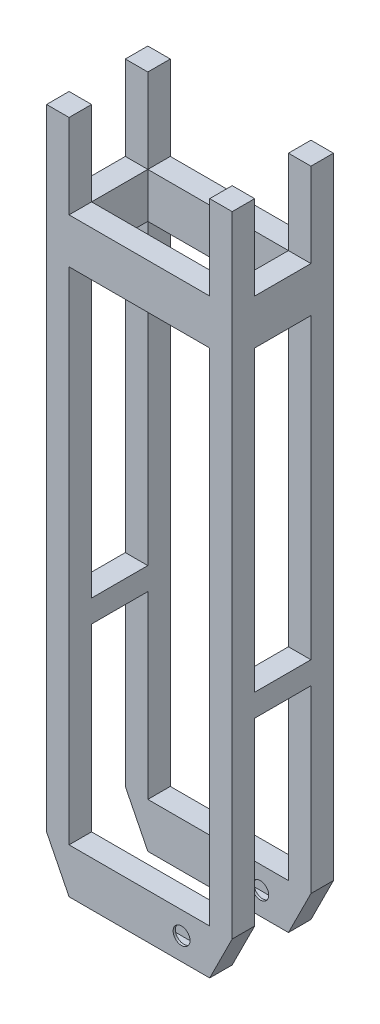
SolidWorks part; units mm, degrees
ref_plane "Plan de face" through (0, 0, 0) normal (0, 0, 1) x (1, 0, 0)
ref_plane "Plan de dessus" through (0, 0, 0) normal (0, 1, 0) x (1, 0, 0)
ref_plane "Plan de droite" through (0, 0, 0) normal (1, 0, 0) x (0, 0, -1)
sketch "Esquisse1" plane through (0, 0, 0) normal (0, 0, 1) x (1, 0, 0)
  line L0 (0, -80) -> (0, -1200)
  line L1 (0, -1200) -> (40, -1280)
  line L2 (40, -1280) -> (290, -1280)
  line L3 (290, -1280) -> (330, -1200)
  line L4 (330, -1200) -> (330, -80)
  line L5 (290, -80) -> (290, -230)
  line L6 (290, -1200) -> (40, -1200)
  line L7 (40, -1200) -> (40, -310)
  line L8 (40, 0) -> (0, 0) construction
  line L9 (330, -80) -> (290, -80)
  line L10 (290, -1200) -> (290, -1280) construction
  line L11 (40, -1200) -> (40, -1280) construction
  line L12 (330, -1200) -> (290, -1200) construction
  line L13 (0, -1200) -> (40, -1200) construction
  line L14 (310, -40) -> (20, -40) construction
  line L15 (290, 0) -> (40, 0) construction
  line L16 (0, -80) -> (40, 0) construction
  line L17 (290, 0) -> (330, -80) construction
  line L18 (330, -80) -> (290, -80) construction
  line L19 (0, -80) -> (40, -80) construction
  line L20 (40, -80) -> (290, -80) construction
  line L21 (290, -80) -> (290, 0) construction
  line L22 (40, 0) -> (40, -80) construction
  line L23 (191.5525, -38.0799) -> (138.4475, -38.0799) construction
  line L24 (165, -38.0799) -> (165, -40) construction
  line L25 (0, 0) -> (0, -80) construction
  line L26 (290, -230) -> (40, -230)
  line L27 (40, -310) -> (290, -310)
  line L28 (290, -310) -> (290, -1200)
  line L29 (40, -230) -> (40, -80)
  line L30 (0, -80) -> (40, -80)
  circle A0 centre (165, -231.2637) radius 195 construction
  circle A1 centre (165, -426.2637) radius 6.75 construction
  circle A2 centre (112.3896, -419.0326) radius 6.75 construction
  circle A3 centre (63.6811, -397.8755) radius 6.75 construction
  circle A4 centre (22.487, -364.3616) radius 6.75 construction
  circle A5 centre (-8.1376, -320.9764) radius 6.75 construction
  circle A6 centre (-25.9214, -270.9376) radius 6.75 construction
  circle A7 centre (-29.5454, -217.9564) radius 6.75 construction
  circle A8 centre (-18.7409, -165.9622) radius 6.75 construction
  circle A9 centre (5.6909, -118.811) radius 6.75 construction
  circle A10 centre (41.9379, -80) radius 6.75 construction
  circle A11 centre (87.3118, -52.4075) radius 6.75 construction
  circle A12 centre (138.4475, -38.0799) radius 6.75 construction
  circle A13 centre (191.5525, -38.0799) radius 6.75 construction
  circle A14 centre (242.6882, -52.4075) radius 6.75 construction
  circle A15 centre (288.0621, -80) radius 6.75 construction
  circle A16 centre (324.3091, -118.811) radius 6.75 construction
  circle A17 centre (348.7409, -165.9622) radius 6.75 construction
  circle A18 centre (359.5454, -217.9564) radius 6.75 construction
  circle A19 centre (355.9214, -270.9376) radius 6.75 construction
  circle A20 centre (338.1376, -320.9764) radius 6.75 construction
  circle A21 centre (307.513, -364.3616) radius 6.75 construction
  circle A22 centre (266.3189, -397.8755) radius 6.75 construction
  circle A23 centre (217.6104, -419.0326) radius 6.75 construction
  point P64 (165, -231.2637)
  dimension "D3" = 390
  dimension "D4" = 13.5
  dimension "D1" = 80
  dimension "D2" = 1280
  dimension "D6" = 40
  dimension "D7" = 40
  dimension "D8" = 80
  dimension "D9" = 80
  dimension "D10" = 230
  dimension "D11" = 330
  dimension "D5" = 23
extrude "Boss.-Extru.1" add sketch "Esquisse1" along normal blind 180 contours L17 L15 L16 L0 L1 L2 L3 L4 L27 L28 L6 L7 L26 L29 L20 L5 region at (20, -92.4455, 0)
sketch "Esquisse2" plane through (0, -80, 0) normal (0, 1, 0) x (1, 0, 0)
  line L1 (290, -40) -> (40, -40)
  line L2 (290, -40) -> (290, -140)
  line L3 (290, -140) -> (40, -140)
  line L4 (40, -40) -> (40, -140)
  line L8 (290, -180) -> (290, 0) construction
  line L9 (40, -180) -> (40, 0) construction
  line L10 (290, -180) -> (40, -180) construction
  line L11 (290, 0) -> (40, 0) construction
  dimension "D1" = 40
  dimension "D2" = 40
extrude "Enlèv. mat.-Extru.1" cut sketch "Esquisse2" against normal through all
sketch "Esquisse3" plane through (290, 0, 0) normal (-1, 0, 0) x (0, 0, 1)
  line L0 (40, -310) -> (40, -230) construction
  line L1 (40, 0) -> (140, 0)
  line L2 (40, 0) -> (40, -230)
  line L3 (40, -230) -> (140, -230)
  line L4 (140, 0) -> (140, -230)
  line L5 (40, -310) -> (140, -310)
  line L6 (40, -310) -> (40, -1280)
  line L7 (40, -1280) -> (140, -1280)
  line L8 (140, -310) -> (140, -1280)
extrude "Enlèv. mat.-Extru.2" cut sketch "Esquisse3" against normal through all both and the other way through all
sketch "Esquisse6" plane through (0, 0, 140) normal (0, 0, -1) x (-1, 0, 0)
  line L0 (-290, -1200) -> (-40, -1200) construction
  line L1 (-40, -1240) -> (-80, -1240) construction
  line L2 (-40, -1240) -> (-40, -1200) construction
  line L3 (-40, -1200) -> (-80, -1200) construction
  line L4 (-80, -1240) -> (-80, -1200) construction
  line L10 (-330, -1200) -> (-330, -310) construction
  line L12 (0, -310) -> (0, -1200) construction
  line L17 (-290, -840) -> (-330, -840)
  line L18 (-290, -840) -> (-290, -880)
  line L19 (-290, -880) -> (-330, -880)
  line L20 (-330, -840) -> (-330, -880)
  line L21 (-290, -1200) -> (-290, -310) construction
  line L22 (-40, -1280) -> (-290, -1280) construction
  line L23 (-40, -310) -> (-40, -230) construction
  line L24 (-40, -840) -> (0, -840)
  line L25 (-40, -840) -> (-40, -880)
  line L26 (-40, -880) -> (0, -880)
  line L27 (0, -840) -> (0, -880)
  dimension "D3" = 40
  dimension "D4" = 40
  dimension "D5" = 40
  dimension "D6" = 400
  dimension "D7" = 40
  dimension "D8" = 400
extrude "Boss.-Extru.2" add sketch "Esquisse6" along normal up to next
shell "Coque1" thickness 4
sketch "Esquisse8" plane through (0, 0, 0) normal (0, 0, -1) x (-1, 0, 0)
  line L0 (-165, -230) -> (-165, -1280) construction
  line L2 (-40, -1280) -> (-290, -1280) construction
  line L3 (-165, -1110.0962) -> (-240, -1240) construction
  line L4 (-20, -1240) -> (-310, -1240) construction
  line L5 (0, -1200) -> (-40, -1280) construction
  line L6 (-290, -1280) -> (-330, -1200) construction
  line L7 (-330, -1200) -> (-330, -80) construction
  line L8 (-290, -230) -> (-40, -230) construction
  circle A0 centre (-240, -1240) radius 15
  circle A1 centre (-90, -1240) radius 15 construction
  dimension "D1" = 30
  dimension "D2" = 30
  dimension "D3" = 90
extrude "Enlèv. mat.-Extru.5" cut sketch "Esquisse8" against normal through all
